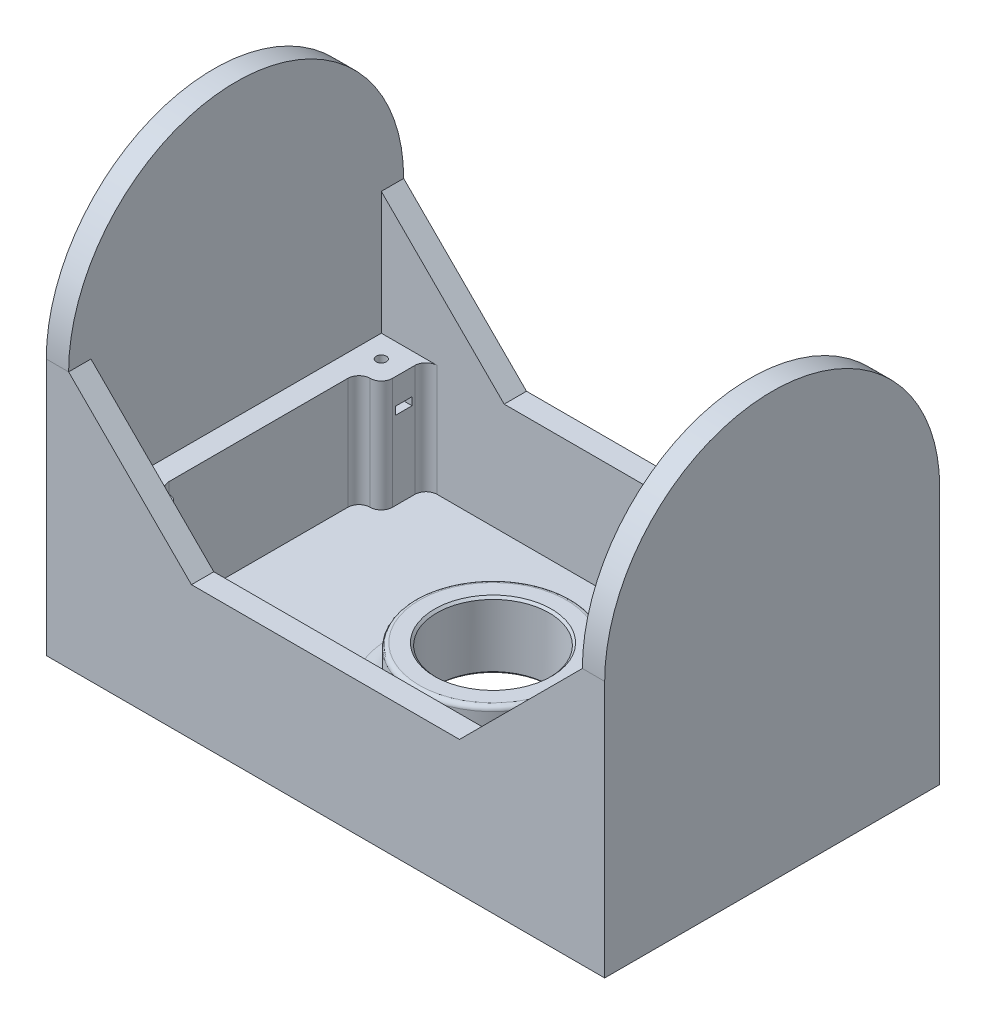
SolidWorks part; units mm, degrees
ref_plane "Front Plane" through (0, 0, 0) normal (0, 0, 1) x (1, 0, 0)
ref_plane "Top Plane" through (0, 0, 0) normal (0, 1, 0) x (1, 0, 0)
ref_plane "Right Plane" through (0, 0, 0) normal (1, 0, 0) x (0, 0, -1)
sketch "Sketch3" plane through (0, 0, 0) normal (0, 1, 0) x (1, 0, 0)
  line L0 (0, -93.3232) -> (0, 91.047) construction
  line L1 (-147.1927, 0) -> (149.8483, 0) construction
  line L3 (-125, -75) -> (125, -75)
  line L4 (-125, -75) -> (-125, 75)
  line L5 (-125, 75) -> (125, 75)
  line L6 (125, -75) -> (125, 75)
  line L7 (-125, -75) -> (125, 75) construction
  line L8 (-125, 75) -> (125, -75) construction
  point P5 (0, 0)
  dimension "D1" = 250
  dimension "D2" = 150
extrude "Boss-Extrude1" add sketch "Sketch3" along normal blind 10
ref_axis "Axis1" through (0, 0, 0) along (0, 1, 0)
sketch "Sketch4" plane through (0, 10, 0) normal (0, 1, 0) x (1, 0, 0)
  circle A0 centre (0, 0) radius 35
  dimension "D1" = 70
extrude "Boss-Extrude2" add sketch "Sketch4" along normal blind 20
sketch "Sketch5" plane through (0, 30, 0) normal (0, 1, 0) x (1, 0, 0)
  circle A0 centre (0, 0) radius 25.15
  dimension "D1" = 50.3
extrude "Cut-Extrude1" cut sketch "Sketch5" against normal through all
chamfer "Chamfer1" distance 1 angle 45 2 edges at (0, 0, 25.15) (0, 30, 25.15)
fillet "Fillet1" radius 2 1 edges at (0, 30, 35)
fillet "Fillet2" radius 10 1 edges at (0, 10, 35)
sketch "Sketch8" plane through (-125, 0, 0) normal (-1, 0, 0) x (0, 0, 1)
  line L0 (-75, 10) -> (-75, 115)
  line L1 (0, 0) -> (0, 254.622) construction
  line L2 (0, 0) -> (0, 96.2107) construction
  line L4 (75, 10) -> (75, 115)
  line L5 (-75, 10) -> (75, 10)
  arc A0 (-75, 115) -> (75, 115) centre (0, 115) cw
  dimension "D2" = 75
extrude "Boss-Extrude3" add sketch "Sketch8" against normal blind 10
mirror "Mirror1" about plane through (0, 0, 0) normal (1, 0, 0) of "Boss-Extrude3"
sketch "Sketch9" plane through (0, 10, 0) normal (0, 1, 0) x (1, 0, 0)
  line L0 (-115, -75) -> (115, -75) construction
  line L1 (115, 75) -> (115, -75) construction
  line L2 (115, 75) -> (-115, 75) construction
  line L3 (-115, -75) -> (-115, 75) construction
  line L4 (-115, -75) -> (115, -75)
  line L5 (115, 75) -> (115, -75)
  line L6 (115, 75) -> (-115, 75)
  line L7 (-115, -75) -> (-115, 75)
  line L8 (105, 65) -> (-105, 65)
  line L9 (-105, -65) -> (-105, 65)
  line L10 (-105, -65) -> (105, -65)
  line L11 (105, 65) -> (105, -65)
  dimension "D1" = 10
extrude "Boss-Extrude4" add sketch "Sketch9" along normal blind 50
sketch "Sketch10" plane through (0, 0, 75) normal (0, 0, 1) x (1, 0, 0)
  line L0 (-115, 115) -> (-60, 60)
  line L1 (-115, 60) -> (115, 60) construction
  line L2 (-60, 60) -> (-115, 60)
  line L3 (-115, 60) -> (-115, 115)
extrude "Boss-Extrude5" add sketch "Sketch10" against normal blind 10
sketch "Sketch11" plane through (0, 10, 0) normal (0, 1, 0) x (1, 0, 0)
  line L0 (-115, -75) -> (-115, 75) construction
  line L6 (-60, -65) -> (-115, -65) construction
  line L7 (-105, -65) -> (-95, -65)
  line L8 (-105, -65) -> (-105, -45)
  line L9 (-105, -45) -> (-95, -45)
  line L10 (-95, -65) -> (-95, -45)
  dimension "D3" = 20
  dimension "D4" = 20
extrude "Boss-Extrude7" add sketch "Sketch11" along normal up to surface (50 mm away) up to face at (-12, 60, 13)
sketch "Sketch13" plane through (0, 60, 0) normal (0, 1, 0) x (1, 0, 0)
  circle A0 centre (-105, -55) radius 2.25
  dimension "D1" = 4.5
extrude "Cut-Extrude2" cut sketch "Sketch13" against normal blind 20
ref_plane "Plane2" through (0, 45, 0) normal (0, 1, 0) x (1, 0, 0)
sketch "Sketch14" plane through (0, 45, 0) normal (0, 1, 0) x (1, 0, 0)
  line L0 (-105, -55) -> (-95, -55) construction
  line L1 (-95, -65) -> (-95, -45) construction
  line L2 (-102.8349, -51.25) -> (-95, -51.25)
  line L4 (-102.8349, -51.25) -> (-107.1651, -51.25)
  line L5 (-107.1651, -51.25) -> (-109.3301, -55)
  line L6 (-109.3301, -55) -> (-107.1651, -58.75)
  line L7 (-107.1651, -58.75) -> (-102.8349, -58.75)
  line L9 (-95, -51.25) -> (-95, -58.75)
  line L10 (-95, -65) -> (-95, -45) construction
  line L11 (-95, -58.75) -> (-102.8349, -58.75)
  line L13 (-101.7524, -53.125) -> (-102.8349, -51.25) [skipped]
  line L14 (-102.8349, -58.75) -> (-101.7524, -56.875) [skipped]
  circle A0 centre (-105, -55) radius 3.75 construction
  dimension "D1" = 7.5
extrude "Cut-Extrude3" cut sketch "Sketch14" along normal blind 3.5
fillet "Fillet3" radius 5 3 edges at (-95, 35, 65) (-105, 35, 45) (-95, 35, 45)
mirror "Mirror2" about plane through (0, 0, 0) normal (0, 0, 1) of "Cut-Extrude3", "Cut-Extrude2", "Boss-Extrude7", "Boss-Extrude5"
mirror "Mirror3" about plane through (0, 0, 0) normal (1, 0, 0) of "Mirror2"
fillet "Fillet4" radius 5 9 edges at (95, 35, 65) (95, 35, 45) (105, 35, 45) (105, 35, -45) (95, 35, -45) (95, 35, -65) (-95, 35, -65) (-95, 35, -45) (-105, 35, -45)
